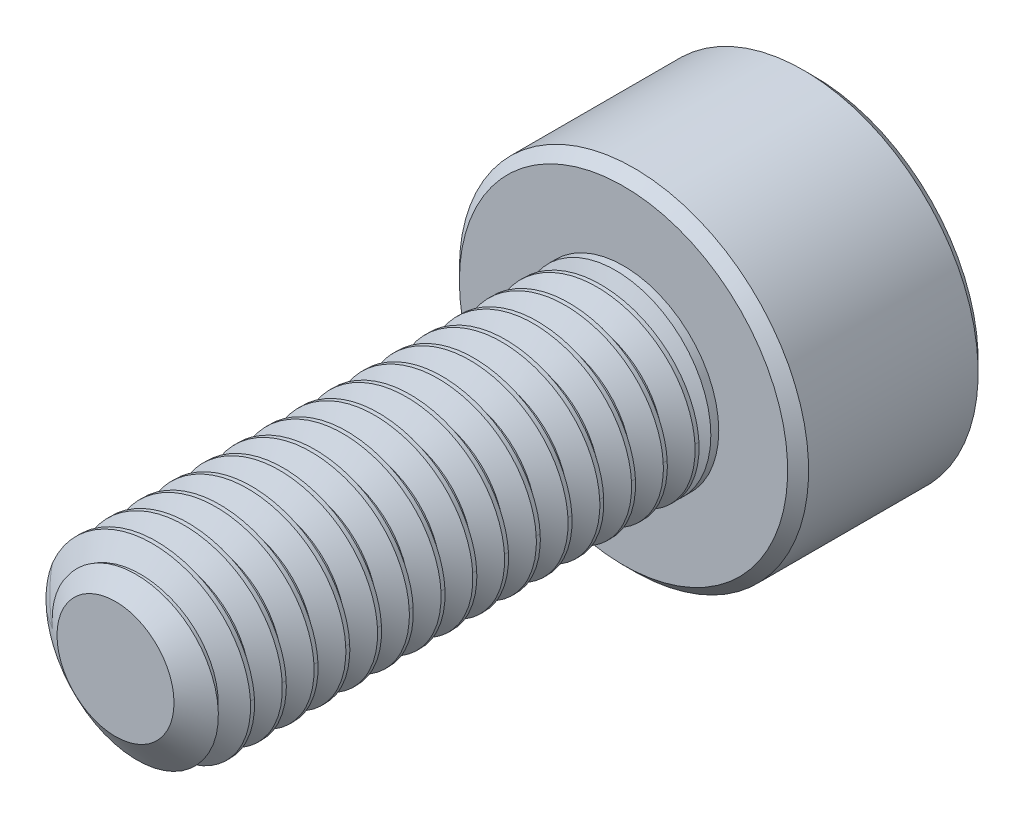
SolidWorks part; units mm, degrees
ref_plane "Front Plane" through (0, 0, 0) normal (0, 0, 1) x (1, 0, 0)
ref_plane "Top Plane" through (0, 0, 0) normal (0, 1, 0) x (1, 0, 0)
ref_plane "Right Plane" through (0, 0, 0) normal (1, 0, 0) x (0, 0, -1)
sketch "Sketch1" plane through (0, 0, 0) normal (0, 0, 1) x (1, 0, 0)
  circle A0 centre (0, 0) radius 1.5
  dimension "OD" = 3
extrude "Extrude1" add sketch "Sketch1" against normal blind 8
sketch "Sketch2" plane through (0, 0, 0) normal (0, 0, 1) x (1, 0, 0)
  circle A0 centre (0, 0) radius 1.5 construction
  circle A1 centre (0, 0) radius 1.5
curve "Helix/Spiral1" pitch 0.5 height 8.5 radius 1.5 centre (0, 0, 0) axis (0, 0, -1) start towards (0, 1, 0) parameters "pitch"=0.5
sketch "Sketch3" plane through (0, 0, 0) normal (1, 0, 0) x (0, 0, -1)
  line L0 (-0.4375, 1.5) -> (-0.25, 1.1752)
  line L1 (-0.25, 1.1752) -> (-0.1875, 1.1752)
  line L2 (-0.1875, 1.1752) -> (0, 1.5)
  line L3 (-0.4375, 1.5) -> (0, 1.5)
  line L4 (-0.2187, 1.5) -> (-0.2187, 1.1752) construction
  line L5 (-0.3437, 1.3376) -> (-0.0937, 1.3376) construction
  line L6 (0, 1.5) -> (0, -1.5) construction
  line L7 (0, -1.5) -> (8, -1.5) construction
  point P11 (2.25, -1.5)
  dimension "D1" = 0.0625
  dimension "D2" = 0.25
  dimension "D3" = 60
  dimension "D4" = 2.25
sweep "Cut-Sweep1" cut profiles "Sketch3" path "Helix/Spiral1" align with end faces yes
sketch "Sketch4" plane through (0, 0, 0) normal (1, 0, 0) x (0, 0, -1)
  line L0 (0.4053, 1.5) -> (0, 0.9212)
  line L1 (0, 0.9212) -> (0, 1.5)
  line L2 (0.4053, 1.5) -> (0, 1.5)
  line L3 (-0.4375, 1.5) -> (0, 1.5) construction
  line L4 (0, 0) -> (7.0209, 0) construction
  dimension "D1" = 55
  dimension "D2" = 0.254
revolve "Cut-Revolve1" cut sketch "Sketch4" angle 360 about L4
sketch "Sketch5" plane through (0, 0, 0) normal (1, 0, 0) x (0, 0, -1)
  line L0 (8, -1.1822) -> (8, 1.0703) construction
  line L1 (8, 1.5) -> (0.1203, 1.5)
  line L2 (8, 1.5) -> (8, 0)
  line L3 (8, 0) -> (0.0001, 0)
  line L4 (0.0001, 1.1698) -> (0.0001, 0)
  line L5 (0.1203, 1.5) -> (0.0001, 1.1698)
  line L6 (0, 0) -> (9.9695, 0) construction
  point P3 (0.0001, 1.5)
  point P10 (0.0001, 1.5)
  dimension "D1" = 0.3302
  dimension "Thread min" = 0.0001
  dimension "D3" = 20
revolve "partially thread" [suppressed] add sketch "Sketch5" angle 360 about L6
sketch "Sketch6" plane through (0, 0, -8) normal (0, 0, -1) x (-1, 0, 0)
  circle A0 centre (0, 0) radius 2.75
  dimension "head dia" = 5.5
extrude "Extrude2" add sketch "Sketch6" along normal blind 3
sketch "Sketch7" plane through (0, 0, -11) normal (0, 0, -1) x (-1, 0, 0)
  line L1 (0, 1.4434) -> (-1.25, 0.7217)
  line L2 (-1.25, 0.7217) -> (-1.25, -0.7217)
  line L3 (-1.25, -0.7217) -> (0, -1.4434)
  line L4 (0, -1.4434) -> (1.25, -0.7217)
  line L5 (1.25, -0.7217) -> (1.25, 0.7217)
  line L6 (1.25, 0.7217) -> (0, 1.4434)
  circle A0 centre (0, 0) radius 1.25 construction
  dimension "hex dia" = 2.5
extrude "Cut-Extrude1" cut sketch "Sketch7" against normal blind 1.875
sketch "Sketch8" plane through (0, 0, -11) normal (0, 0, -1) x (-1, 0, 0)
  circle A0 centre (0, 0) radius 1.4434
extrude "Cut-Extrude2" cut sketch "Sketch8" against normal through all draft 45
chamfer "Chamfer1" distance 0.165 angle 45 2 edges at (-2.75, 0, -11) (-2.75, 0, -8)
sketch "Sketch9" plane through (0, 0, 0) normal (1, 0, 0) x (0, 0, -1)
  line L0 (0, 1.5) -> (0, -1.5) construction
  line L1 (2.75, 1.5) -> (2.75, -1.5) construction
  dimension "D1" = 2.75
sketch "Sketch10" plane through (0, 0, 0) normal (1, 0, 0) x (0, 0, -1)
  line L0 (8, 1.5) -> (8, 0)
  line L1 (8, 1.5) -> (7.875, 1.5)
  line L2 (7.875, 1.5) -> (7.2537, 0)
  line L3 (8, 0) -> (7.2537, 0)
  line L4 (8, 2.585) -> (8, -2.585) construction
  dimension "D1" = 22.5
  dimension "D2" = 0.125
revolve "Revolve1" add sketch "Sketch10" angle 360 about L3
equation "\"D3@Helix/Spiral1\" = \"screw length@Extrude1\"+\"pitch@Helix/Spiral1\""
equation "\"D1@Sketch3\" = \"pitch@Helix/Spiral1\"*.125"
equation "\"D2@Sketch3\" = \"pitch@Helix/Spiral1\"*.5"
equation "\"D1@Cut-Extrude1\" = \"hex dia@Sketch7\"*.75"
equation "\"D1@Chamfer1\" = \"head dia@Sketch6\"*.03"
equation "\"D1@Sketch9\" = \"pitch@Helix/Spiral1\"*5.5"
equation "\"D2@Sketch10\" = \"pitch@Helix/Spiral1\"*.25"
equation "\"D4@Sketch3\" = \"pitch@Helix/Spiral1\"*4.50"
